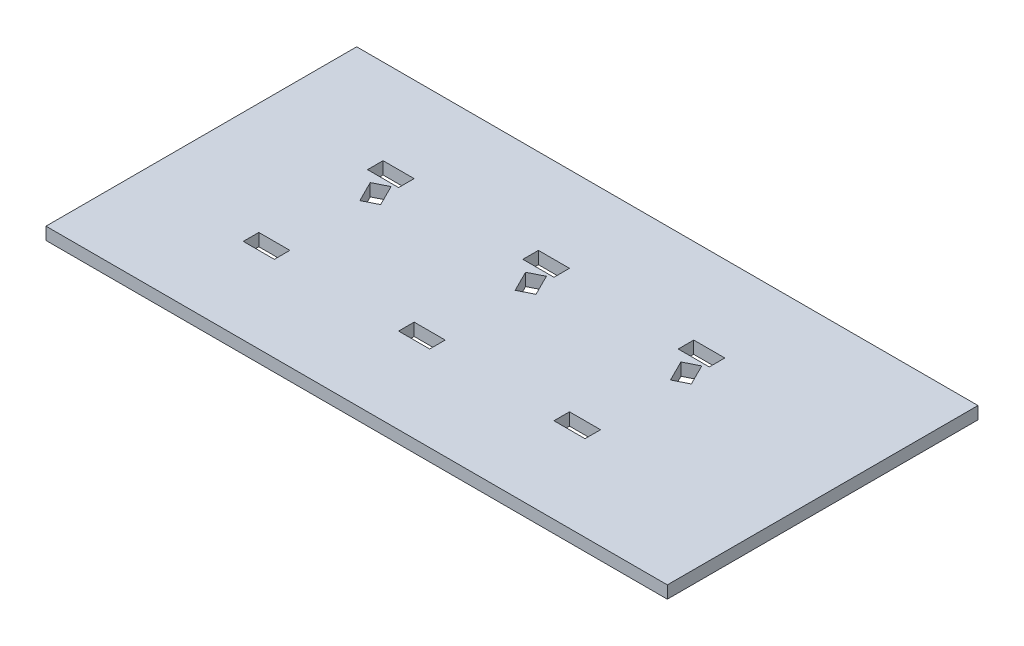
SolidWorks part; units mm, degrees
ref_plane "Front Plane" through (0, 0, 0) normal (0, 0, 1) x (1, 0, 0)
ref_plane "Top Plane" through (0, 0, 0) normal (0, 1, 0) x (1, 0, 0)
ref_plane "Right Plane" through (0, 0, 0) normal (1, 0, 0) x (0, 0, -1)
sketch "Sketch1" plane through (0, 0, 0) normal (0, 1, 0) x (1, 0, 0)
  line L1 (-50.8, -25.4) -> (50.8, -25.4)
  line L2 (-50.8, -25.4) -> (-50.8, 25.4)
  line L3 (-50.8, 25.4) -> (50.8, 25.4)
  line L4 (50.8, -25.4) -> (50.8, 25.4)
  line L5 (0, 25.4) -> (0, -25.4) construction
  line L6 (-50.8, 0) -> (50.8, 0) construction
  point P0 (0, 0)
  dimension "D1" = 50.8
  dimension "D2" = 101.6
extrude "Boss-Extrude1" add sketch "Sketch1" along normal blind 2.032
sketch "Sketch2" plane through (0, 2.032, 0) normal (0, 1, 0) x (1, 0, 0)
  line L0 (-3.3577, 3.8746) -> (-1.0859, 5.0107)
  line L1 (-3.3577, 3.8746) -> (-5.0618, 7.2822)
  line L2 (-1.0859, 5.0107) -> (-2.7901, 8.4183)
  line L3 (-5.0618, 7.2822) -> (-2.7901, 8.4183)
  line L5 (-1.1176, 0) -> (1.1176, 0) construction
  circle A0 centre (0, 0) radius 5.127 construction
  dimension "D1" = 10.254
  dimension "D3" = 3.81
  dimension "D4" = 2.54
  dimension "D2" = 63.43
extrude "Cut-Extrude1" cut sketch "Sketch2" against normal through all contours L3 L1 L0 L2 region at (-3.0739, 2.032, -6.1464)
sketch "Sketch3" plane through (0, 2.032, 0) normal (0, 1, 0) x (1, 0, 0)
  line L0 (-7.112, 8.89) -> (-2.032, 8.89)
  line L1 (-7.112, 8.89) -> (-7.112, 11.43)
  line L2 (-2.032, 8.89) -> (-2.032, 11.43)
  line L3 (-7.112, 11.43) -> (-2.032, 11.43)
  line L4 (-1.1176, 0) -> (1.1176, 0) construction
  line L5 (0, -1.1176) -> (0, 1.1176) construction
  dimension "D1" = 2.54
  dimension "D2" = 5.08
  dimension "D3" = 2.032
  dimension "D4" = 8.89
extrude "Cut-Extrude2" cut sketch "Sketch3" against normal through all
mirror "Mirror1" about plane through (0, 0, 0) normal (0, 0, 1) of "Cut-Extrude2"
pattern_linear "LPattern1" count 2 spacing 25.4 along (-1, 0, 0) count 2 spacing 25.4 along (1, 0, 0) of "Cut-Extrude1", "Cut-Extrude2", "Mirror1"
equation "\"Arrow Height\"= 1in"
equation "\"Button Height\"= 2in"
equation "\"Button Width\"= 4in"
equation "\"Haptic Diameter\"= 10mm"
equation "\"Haptic Thickness\"= 2.7mm"
equation "\"D1@Sketch1\"=\"Button Height\""
equation "\"D2@Sketch1\"=\"Button Width\""
equation "\"D1@Sketch2\"=\"Haptic Diameter\"+.01in"
equation "\"Arrow Spacing\"= 1in"
equation "\"Arrow Width\" = 0.75in"
equation "\"Haptic Wire Angle\" = 63.43"
equation "\"Haptic Wire Width\" = .1in"
equation "\"Hatic Wire Height\"= .15in"
equation "\"D2@Sketch2\"=\"Haptic Wire Angle\""
equation "\"D4@Sketch2\"=\"Haptic Wire Width\""
equation "\"D3@Sketch2\"=\"Hatic Wire Height\""
